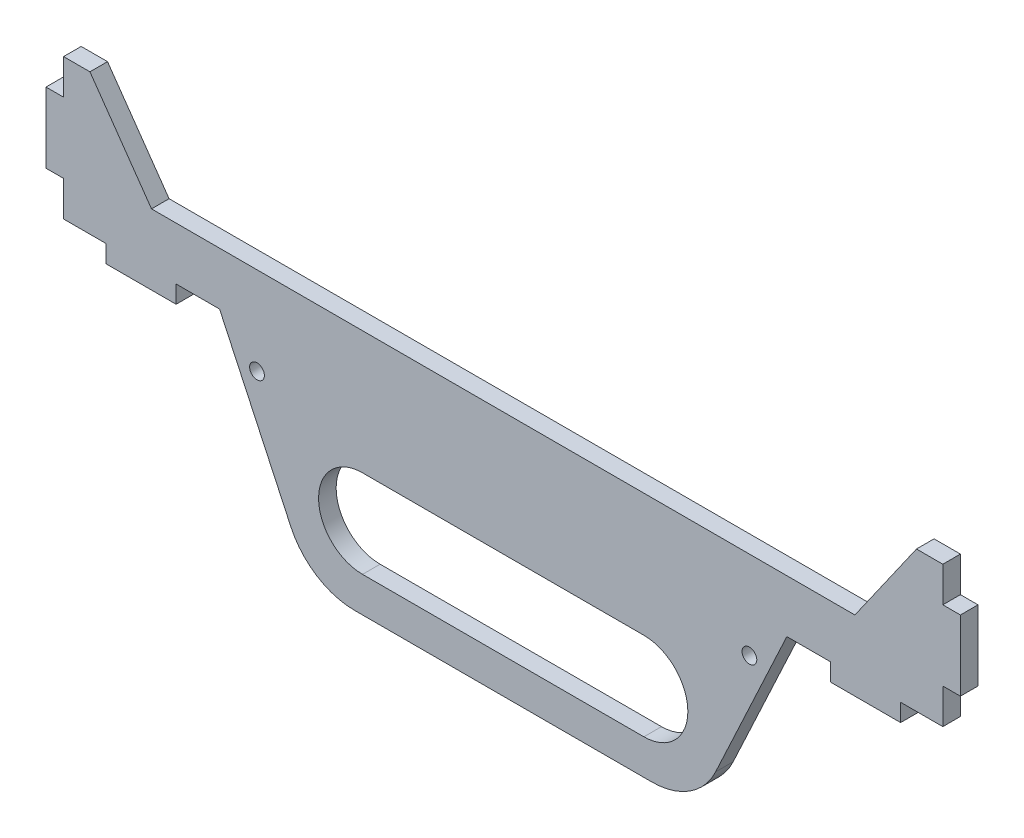
SolidWorks part; units mm, degrees
ref_plane "Front Plane" through (0, 0, 0) normal (0, 0, 1) x (1, 0, 0)
ref_plane "Top Plane" through (0, 0, 0) normal (0, 1, 0) x (1, 0, 0)
ref_plane "Right Plane" through (0, 0, 0) normal (1, 0, 0) x (0, 0, -1)
sketch "Sketch1" plane through (0, 0, 0) normal (0, 0, 1) x (1, 0, 0)
  line L0 (0, 0) -> (7.4948, 0)
  line L2 (7.4948, 0) -> (25, -25)
  line L3 (25, -25) -> (225, -25)
  line L4 (225, -25) -> (242.5052, 0)
  line L5 (242.5052, 0) -> (250, 0)
  line L7 (250, -40) -> (238, -40)
  line L9 (205.6469, -40) -> (180, -95)
  line L10 (180, -95) -> (70, -95)
  line L11 (70, -95) -> (44.3531, -40)
  line L12 (44.3531, -40) -> (32, -40)
  line L13 (0, -40) -> (0, -30)
  line L14 (0, -30) -> (-5, -30)
  line L16 (-5, -30) -> (-5, -10)
  line L17 (-5, -10) -> (0, -10)
  line L18 (0, -10) -> (0, 0)
  line L19 (250, -40) -> (250, -30)
  line L20 (250, -30) -> (255, -30)
  line L22 (255, -30) -> (255, -10)
  line L23 (255, -10) -> (250, -10)
  line L24 (250, -10) -> (250, 0)
  line L25 (85, -72.5) -> (165, -72.5) construction
  line L26 (85, -60) -> (165, -60)
  line L27 (85, -85) -> (165, -85)
  line L29 (218, -40) -> (205.6469, -40)
  line L30 (12, -40) -> (0, -40)
  line L31 (218, -40) -> (218, -45)
  line L32 (218, -45) -> (238, -45)
  line L33 (238, -40) -> (238, -45)
  line L35 (12, -40) -> (12, -45)
  line L36 (12, -45) -> (32, -45)
  line L37 (32, -40) -> (32, -45)
  arc A0 (85, -60) -> (85, -85) centre (85, -72.5) ccw
  arc A1 (165, -85) -> (165, -60) centre (165, -72.5) ccw
  point P34 (125, -72.5)
  dimension "D1" = 12.5
  dimension "D5" = 32
  dimension "D2" = 7.4948
  dimension "D3" = 12
  dimension "D4" = 25
  dimension "D6" = 44.3531
  dimension "D7" = 70
  dimension "D8" = 85
  dimension "D9" = 125
  dimension "D10" = 180
  dimension "D11" = 255
  dimension "D12" = 10
  dimension "D13" = 25
  dimension "D14" = 72.5
  dimension "D15" = 95
extrude "Boss-Extrude1" add sketch "Sketch1" along normal blind 5
fillet "Fillet1" radius 20 2 edges at (70, -95, 2.5) (180, -95, 2.5)
sketch "Sketch3" plane through (0, 0, 5) normal (0, 0, 1) x (1, 0, 0)
  line L0 (225, -25) -> (25, -25) construction
  line L1 (0, -50) -> (0, -20) construction
  circle A0 centre (55, -50) radius 2.1
  circle A1 centre (55, -50) radius 4 construction
  dimension "D1" = 4.2
  dimension "D2" = 8
  dimension "D3" = 25
  dimension "D4" = 55
extrude "Cut-Extrude1" cut sketch "Sketch3" against normal blind 5
ref_plane "Plane1" through (125, 0, 0) normal (-1, 0, 0) x (0, 0, 1)
mirror "Mirror1" about plane through (125, 0, 0) normal (-1, 0, 0) of "Cut-Extrude1"
